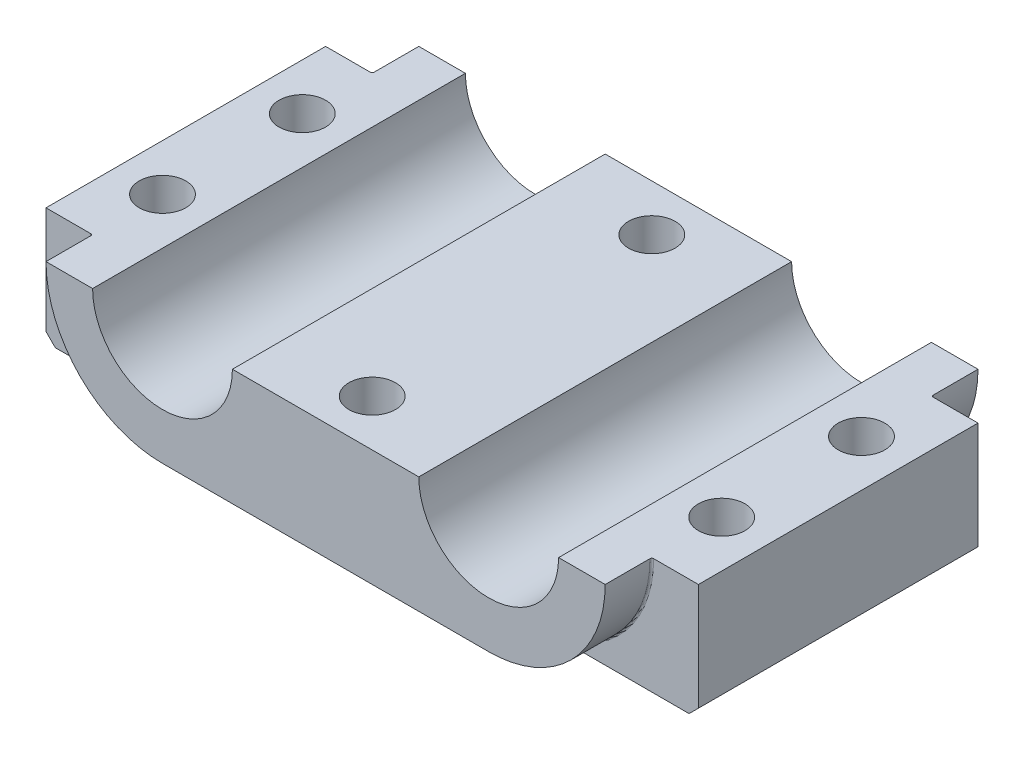
SolidWorks part; units mm, degrees
ref_plane "Спереди" through (0, 0, 0) normal (0, 0, 1) x (1, 0, 0)
ref_plane "Сверху" through (0, 0, 0) normal (0, 1, 0) x (1, 0, 0)
ref_plane "Справа" through (0, 0, 0) normal (1, 0, 0) x (0, 0, -1)
sketch "Эскиз1" plane through (0, 0, 0) normal (0, 0, 1) x (1, 0, 0)
  line L0 (0, 0) -> (17.5, 0) construction
  line L1 (17.5, -12.5) -> (-17.5, -12.5)
  line L2 (0, -12.5) -> (0, 0) construction
  line L3 (-10, 0) -> (10, 0)
  line L4 (25, 0) -> (30, 0)
  line L5 (-25, 0) -> (-30, 0)
  arc A0 (10, 0) -> (25, 0) centre (17.5, 0) ccw
  arc A1 (17.5, -12.5) -> (30, 0) centre (17.5, 0) ccw
  arc A2 (-17.5, -12.5) -> (-30, 0) centre (-17.5, 0) cw
  arc A3 (-10, 0) -> (-25, 0) centre (-17.5, 0) cw
  dimension "D1" = 7.5
  dimension "D2" = 12.5
  dimension "D3" = 17.5
extrude "Бобышка-Вытянуть1" add sketch "Эскиз1" along normal blind 20 and the other way blind 20
sketch "Эскиз2" plane through (0, 0, 0) normal (0, 0, 1) x (1, 0, 0)
  line L0 (30, 0) -> (35, 0)
  line L1 (35, 0) -> (35, -12.5)
  line L2 (35, -12.5) -> (17.5, -12.5)
  line L3 (17.5, -12.5) -> (-17.5, -12.5)
  line L4 (-17.5, -12.5) -> (17.5, -12.5)
  line L5 (30, 0) -> (25, 0)
  line L6 (10, 0) -> (-10, 0)
  line L7 (-25, 0) -> (-30, 0)
  line L8 (-17.5, -12.5) -> (17.5, -12.5) construction
  line L9 (30, 0) -> (25, 0) construction
  line L10 (10, 0) -> (-10, 0) construction
  line L11 (-25, 0) -> (-30, 0) construction
  line L12 (-10, 0) -> (10, 0)
  line L13 (25, 0) -> (30, 0)
  line L14 (0, 0) -> (0, -12.5) construction
  line L15 (-35, -12.5) -> (-17.5, -12.5)
  line L16 (-35, 0) -> (-35, -12.5)
  line L17 (-30, 0) -> (-35, 0)
  line L18 (-25, 0) -> (-30, 0)
  arc A0 (-10, 0) -> (-25, 0) centre (-17.5, 0) cw
  arc A4 (-30, 0) -> (-17.5, -12.5) centre (-17.5, 0) ccw
  arc A5 (17.5, -12.5) -> (30, 0) centre (17.5, 0) ccw
  arc A6 (10, 0) -> (25, 0) centre (17.5, 0) ccw
  arc A7 (-25, 0) -> (-10, 0) centre (-17.5, 0) ccw
  arc A8 (-30, 0) -> (-17.5, -12.5) centre (-17.5, 0) ccw construction
  arc A9 (17.5, -12.5) -> (30, 0) centre (17.5, 0) ccw construction
  arc A10 (10, 0) -> (25, 0) centre (17.5, 0) ccw
  arc A11 (-25, 0) -> (-10, 0) centre (-17.5, 0) ccw construction
  dimension "D2" = 35
  dimension "D1" = 0
extrude "Бобышка-Вытянуть2" add sketch "Эскиз2" along normal blind 15 and the other way blind 15
sketch "Эскиз3" plane through (0, 0, 0) normal (0, 1, 0) x (1, 0, 0)
  line L0 (0, 0) -> (30, 0) construction
  line L1 (35, 15) -> (35, -15) construction
  line L2 (0, 0) -> (0, -15) construction
  line L3 (30, 0) -> (30, -7.5) construction
  line L4 (35, 15) -> (35, -15) construction
  circle A0 centre (0, -15) radius 2.25
  circle A1 centre (30, -7.5) radius 2.25
  circle A2 centre (-30, -7.5) radius 2.25
  circle A3 centre (30, 7.5) radius 2.25
  circle A4 centre (0, 15) radius 2.25
  circle A5 centre (-30, 7.5) radius 2.25
  point P8 (30, -7.5)
  point P9 (-30, -7.5)
  point P11 (-30, 7.5)
  point P12 (30, 7.5)
  point P13 (0, 15)
  dimension "D4" = 4.5
  dimension "D5" = 4.5
  dimension "D6" = 4.5
  dimension "D1" = 5
  dimension "D2" = 15
  dimension "D3" = 7.5
chamfer "Фаска1" distance 1 angle 45 2 edges at (-35, -12.5, 0) (35, -12.5, 0)
hole_wizard "Отверстия под штифты Ø5.0 мм1" positions "Эскиз4" profile "Эскиз5" hole size "Ø5.0" standard "ISO" end condition through all
sketch "Эскиз4" plane through (0, 0, 0) normal (0, 1, 0) x (1, 0, 0)
  point P0 (0, 15)
  point P3 (0, -15)
  point P6 (-30, -7.5)
  point P9 (-30, 7.5)
  point P12 (30, 7.5)
  point P15 (30, -7.5)
sketch "Эскиз5" plane through (0, 0, -15) normal (1, 0, 0) x (0, 0, 1)
  line L0 (0, 0) -> (0, 12.5)
  line L1 (0, 12.5) -> (2.5, 12.5)
  line L2 (2.5, 12.5) -> (2.5, 0)
  line L5 (2.5, 0) -> (0, 0)
  line L11 (0, -6.35) -> (0, 107.95) construction
  dimension "Диаметр сквозного отверстия" = 5
  dimension "Глубина сквозного отверстия" = 12.5
fillet "Скругление1" radius 0.2 4 edges at (26.3388, -8.8388, -15) (-26.3388, -8.8388, -15) (-26.3388, -8.8388, 15) (26.3388, -8.8388, 15)
